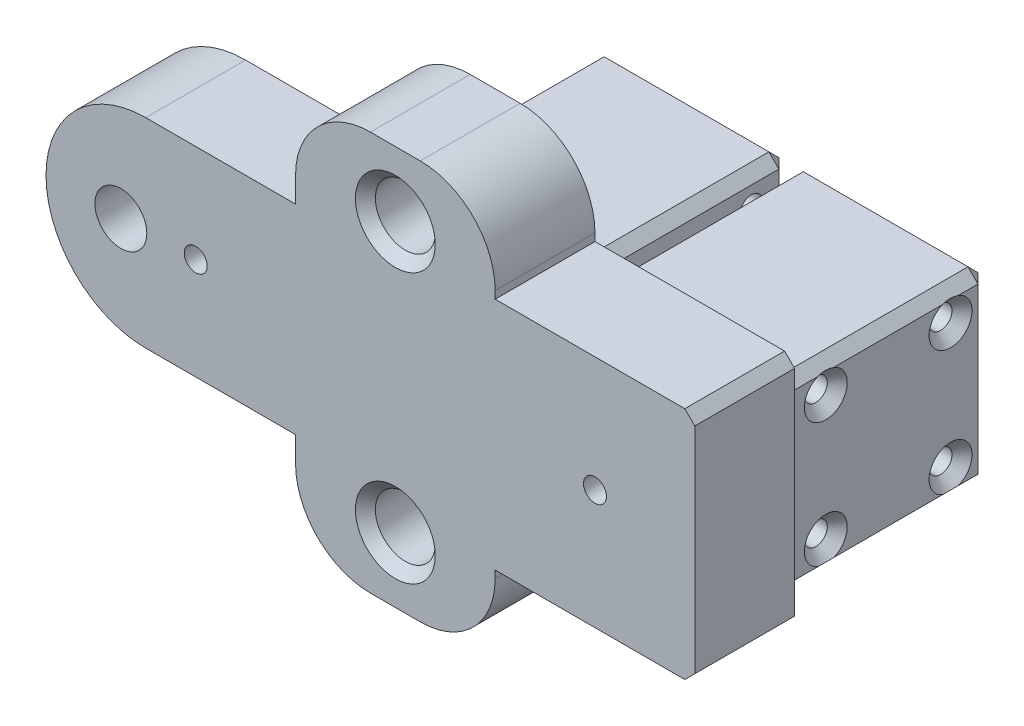
SolidWorks part; units mm, degrees
material "ABS PC"
ref_plane "Front Plane" through (0, 0, 0) normal (0, 0, 1) x (1, 0, 0)
ref_plane "Top Plane" through (0, 0, 0) normal (0, 1, 0) x (1, 0, 0)
ref_plane "Right Plane" through (0, 0, 0) normal (1, 0, 0) x (0, 0, -1)
sketch "Sketch1" plane through (0, 0, 0) normal (0, 0, 1) x (1, 0, 0)
  line L17 (23.495, 46.99) -> (23.495, 0) construction
  line L22 (0, 0) -> (46.99, 0)
  line L23 (0, 0) -> (0, 46.99)
  line L24 (0, 46.99) -> (46.99, 46.99)
  line L25 (46.99, 0) -> (46.99, 46.99)
  line L26 (0, 23.495) -> (46.99, 23.495) construction
  point P18 (0, 0)
  dimension "D1" = 46.99
  dimension "D2" = 46.99
extrude "Boss-Extrude2" add sketch "Sketch1" along normal blind 50.8
sketch "Sketch3" plane through (0, 0, 50.8) normal (0, 0, 1) x (1, 0, 0)
  line L2 (-2.2225, 53.34) -> (-2.2225, -6.35)
  line L4 (48.5775, 53.34) -> (48.5775, -6.35)
  line L5 (46.99, 0) -> (46.99, 46.99) construction
  line L7 (23.1775, 72.39) -> (23.1775, -25.4) construction
  line L8 (-2.2225, 23.495) -> (48.5775, 23.495) construction
  line L9 (-2.2225, -6.35) -> (48.5775, -6.35)
  line L10 (-2.2225, 53.34) -> (48.5775, 53.34)
  line L11 (0, 0) -> (46.99, 0) construction
  point P19 (-2.2225, 72.39)
  dimension "D1" = 50.8
  dimension "D2" = 1.5875
  dimension "D3" = 59.69
  dimension "D4" = 6.35
extrude "Boss-Extrude3" add sketch "Sketch3" along normal blind 25.4
sketch "Sketch4" plane through (0, 0, 0) normal (-1, 0, 0) x (0, 0, 1)
  line L3 (0, 46.99) -> (50.8, 0) construction
  line L4 (50.8, 46.99) -> (0, 46.99) construction
  line L5 (50.8, 46.99) -> (0, 0) construction
  line L6 (0, 23.495) -> (50.8, 23.495) construction
  line L7 (0, 46.99) -> (0, 0) construction
  line L8 (50.8, 46.99) -> (50.8, 0) construction
  line L9 (25.4, 46.99) -> (25.4, 0) construction
  line L10 (50.8, 0) -> (0, 0) construction
  circle A0 centre (41.275, 39.37) radius 2.921
  circle A1 centre (41.275, 7.62) radius 2.921
  circle A2 centre (9.525, 7.62) radius 2.921
  circle A3 centre (9.525, 39.37) radius 2.921
  dimension "D2" = 5.842
  dimension "D1" = 15.875
  dimension "D3" = 15.875
sketch "Sketch8" plane through (-2.2225, 0, 0) normal (-1, 0, 0) x (0, 0, 1)
  line L6 (50.8, 23.495) -> (76.2, 23.495) construction
  line L7 (50.8, 53.34) -> (50.8, -6.35) construction
  line L8 (76.2, 53.34) -> (76.2, -6.35) construction
  line L10 (50.8, 48.895) -> (76.2, 48.895)
  line L11 (50.8, 48.895) -> (50.8, -1.905)
  line L12 (50.8, -1.905) -> (76.2, -1.905)
  line L13 (76.2, 48.895) -> (76.2, -1.905)
  dimension "D1" = 50.8
  dimension "D2" = 25.4
extrude "Boss-Extrude4" add sketch "Sketch8" along normal blind 114.3
sketch "Sketch9" plane through (0, 0, 50.8) normal (0, 0, -1) x (-1, 0, 0)
  line L0 (0, 46.99) -> (0, 0) construction
  line L1 (3.683, 46.99) -> (50.673, 46.99)
  line L2 (3.683, 46.99) -> (3.683, 0)
  line L3 (3.683, 0) -> (50.673, 0)
  line L4 (50.673, 46.99) -> (50.673, 0)
  line L5 (-46.99, 46.99) -> (0, 46.99) construction
  line L6 (0, 0) -> (-46.99, 0) construction
  dimension "D2" = 3.683
extrude "Boss-Extrude5" add sketch "Sketch9" along normal blind 50.8
extrude "Cut-Extrude4" cut sketch "Sketch4" against normal through all both and the other way through all
sketch "Sketch10" plane through (0, 0, 76.2) normal (0, 0, 1) x (1, 0, 0)
  line L0 (-116.5225, 48.895) -> (-2.2225, 48.895) construction
  line L1 (-116.5225, -1.905) -> (-116.5225, 48.895) construction
  circle A0 centre (-97.4725, 23.495) radius 6.604
  dimension "D1" = 13.208
  dimension "D2" = 25.4
  dimension "D3" = 19.05
extrude "Cut-Extrude5" cut sketch "Sketch10" against normal through all
fillet "Fillet2" radius 25.4 2 edges at (-116.5225, -1.905, 63.5) (-116.5225, 48.895, 63.5)
sketch "Sketch11" plane through (0, 0, 76.2) normal (0, 0, 1) x (1, 0, 0)
  line L1 (48.5775, -6.35) -> (48.5775, 53.34) construction
  circle A0 centre (23.1775, 23.9878) radius 2.921
  circle A1 centre (-27.6225, 23.9878) radius 2.921
  circle A2 centre (-78.4225, 23.9878) radius 2.921
  dimension "D1" = 5.842
  dimension "D2" = 50.8
  dimension "D3" = 50.8
  dimension "D4" = 25.4
extrude "Cut-Extrude6" cut sketch "Sketch11" against normal through all
sketch "Sketch12" plane through (0, 0, 0) normal (0, 0, -1) x (-1, 0, 0)
  circle A0 centre (-23.1775, 23.9878) radius 5.08
  circle A1 centre (27.6225, 23.9878) radius 5.08
  dimension "D1" = 10.16
extrude "Cut-Extrude7" cut sketch "Sketch12" against normal blind 57.15
sketch "Sketch15" plane through (0, 0, 50.8) normal (0, 0, -1) x (-1, 0, 0)
  circle A0 centre (78.4225, 23.9878) radius 4.445
  dimension "D1" = 8.89
extrude "Cut-Extrude8" cut sketch "Sketch15" against normal blind 12.7
sketch "Sketch16" plane through (0, 0, 76.2) normal (0, 0, 1) x (1, 0, 0)
  line L0 (-21.2725, 74.295) -> (-33.9725, 74.295)
  line L1 (-53.0225, 55.245) -> (-53.0225, -8.255)
  line L2 (-33.9725, -27.305) -> (-21.2725, -27.305)
  line L3 (-2.2225, -8.255) -> (-2.2225, 55.245)
  line L4 (-91.1225, 48.895) -> (-2.2225, 48.895) construction
  line L5 (-91.1225, -1.905) -> (-2.2225, -1.905) construction
  arc A0 (-53.0225, -8.255) -> (-33.9725, -27.305) centre (-33.9725, -8.255) ccw
  arc A1 (-21.2725, -27.305) -> (-2.2225, -8.255) centre (-21.2725, -8.255) ccw
  arc A2 (-2.2225, 55.245) -> (-21.2725, 74.295) centre (-21.2725, 55.245) ccw
  arc A3 (-33.9725, 74.295) -> (-53.0225, 55.245) centre (-33.9725, 55.245) ccw
  circle A4 centre (-27.6225, 57.785) radius 7.62
  circle A5 centre (-27.6225, -10.795) radius 7.62
  point P15 (-2.2225, 74.295)
  point P18 (-53.0225, 74.295)
  point P23 (0, 0)
  point P24 (-27.6225, 74.295)
  dimension "D4" = 19.05
  dimension "D5" = 15.24
  dimension "D1" = 50.8
  dimension "D2" = 25.4
  dimension "D3" = 25.4
  dimension "D6" = 8.89
  dimension "D7" = 8.89
extrude "Boss-Extrude6" add sketch "Sketch16" against normal blind 25.4
chamfer "Chamfer1" distance 2.54 angle 45 33 edges at (46.99, 7.62, 12.446) (46.99, 7.62, 44.196) (46.99, 39.37, 44.196) (46.99, 39.37, 12.446) (-50.673, 10.541, 9.525) (-50.673, 10.541, 41.275) (-50.673, 42.291, 9.525) (-50.673, 42.291, 41.275) (18.0975, 23.9878, 0) (-32.7025, 23.9878, 0) (-20.0025, -10.795, 50.8) (-20.0025, 57.785, 50.8) (-20.0025, 57.785, 76.2) (-20.0025, -10.795, 76.2) (-104.0765, 23.495, 50.8) (0, 46.99, 25.4) (0, 0, 25.4) (23.495, 0, 0) (46.99, 0, 25.4) (46.99, 23.495, 0) (46.99, 46.99, 25.4) (23.495, 46.99, 0) (0, 23.495, 0) (-50.673, 46.99, 25.4) (-3.683, 46.99, 25.4) (-50.673, 0, 25.4) (-3.683, 0, 25.4) (-27.178, 0, 0) (-3.683, 23.495, 0) (-50.673, 23.495, 0) (-27.178, 46.99, 0) (48.5775, -6.35, 63.5) (48.5775, 53.34, 63.5)
